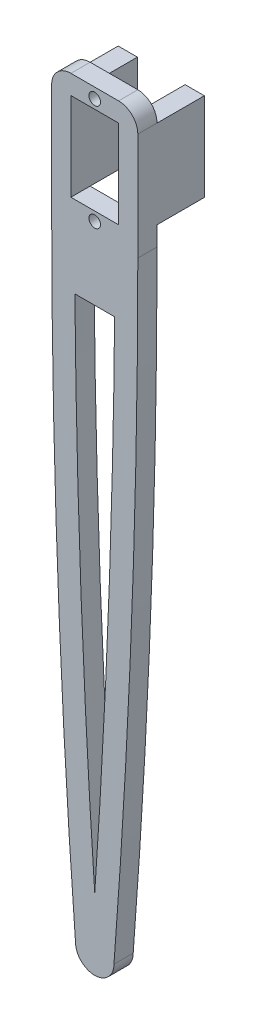
SolidWorks part; units mm, degrees
ref_plane "Front Plane" through (0, 0, 0) normal (0, 0, 1) x (1, 0, 0)
ref_plane "Top Plane" through (0, 0, 0) normal (0, 1, 0) x (1, 0, 0)
ref_plane "Right Plane" through (0, 0, 0) normal (1, 0, 0) x (0, 0, -1)
sketch "Sketch1" plane through (0, 0, 0) normal (0, 0, 1) x (1, 0, 0)
  line L0 (0, -16.45) -> (0, -173.55) construction
  line L1 (-6.2, 16.45) -> (6.2, 16.45)
  line L2 (-11.2, 11.45) -> (-11.2, -16.45)
  line L4 (11.2, 11.45) -> (11.2, -16.45)
  line L5 (-11.2, 16.45) -> (11.2, -16.45) construction
  line L6 (-11.2, -16.45) -> (11.2, 16.45) construction
  arc A1 (-5, -178.55) -> (5, -178.55) centre (0, -178.55) ccw
  arc A2 (-11.2, -16.45) -> (-5, -178.55) centre (2110.9653, -16.45) ccw
  arc A3 (11.2, -16.45) -> (5, -178.55) centre (-2110.9653, -16.45) cw
  arc A4 (11.2, 11.45) -> (6.2, 16.45) centre (6.2, 11.45) ccw
  arc A5 (-6.2, 16.45) -> (-11.2, 11.45) centre (-6.2, 11.45) ccw
  point P0 (0, 0)
  dimension "D4" = 5
  dimension "D1" = 32.9
  dimension "D2" = 22.4
  dimension "D3" = 162.1
extrude "Boss-Extrude2" add sketch "Sketch1" along normal blind 5
sketch "Sketch4" plane through (0, 0, 5) normal (0, 0, 1) x (1, 0, 0)
  line L1 (-6.2, 11.45) -> (6.2, 11.45)
  line L2 (-6.2, 11.45) -> (-6.2, -11.45)
  line L3 (-6.2, -11.45) -> (6.2, -11.45)
  line L4 (6.2, 11.45) -> (6.2, -11.45)
  line L5 (-6.2, 11.45) -> (6.2, -11.45) construction
  line L6 (-6.2, -11.45) -> (6.2, 11.45) construction
  point P0 (0, 0)
  dimension "D1" = 22.9
  dimension "D2" = 12.4
extrude "Cut-Extrude1" cut sketch "Sketch4" against normal blind 5
sketch "Sketch5" plane through (0, 0, 5) normal (0, 0, 1) x (1, 0, 0)
  line L0 (0, 0) -> (0, 13.8) construction
  line L1 (0, 0) -> (0, -13.8) construction
  circle A0 centre (0, 13.8) radius 1.5
  circle A1 centre (0, -13.8) radius 1.5
  dimension "D1" = 13.8
  dimension "D2" = 13.8
extrude "Cut-Extrude2" cut sketch "Sketch5" against normal blind 5
sketch3d "3DSketch1"
  line L6 (-5.1604, -32.6864, 5) -> (5.1604, -32.6864, 5)
  spline S2 degree 5 poles (-5.1604, -32.6864, 5) (-5.1261, -37.5289, 5) (-5.0708, -42.3713, 5) (-4.9981, -47.2135, 5) (-4.7659, -60.1446, 5) (-4.4569, -73.0738, 5) (-4.2293, -81.1606, 5) (-3.6967, -97.3316, 5) (-2.9925, -113.496, 5) (-2.6018, -121.5766, 5) (-1.8933, -135.0415, 5) (-1.1015, -148.5022, 5) (-0.7667, -153.8853, 5) (-0.4048, -159.3358, 5) (-0.0148, -164.7842, 5) (-0.0099, -164.8531, 5) (-0.0049, -164.922, 5) (0, -164.9909, 5) knots 0.10922 0.10922 0.10922 0.10922 0.10922 0.10922 0.272094 0.272094 0.272094 0.544187 0.544187 0.544187 0.816281 0.816281 0.816281 0.997676 0.997676 0.997676 1 1 1 1 1 1
  spline S3 degree 5 poles (0, -164.9909, 5) (0.0049, -164.922, 5) (0.0099, -164.8531, 5) (0.0148, -164.7842, 5) (0.4048, -159.3358, 5) (0.7667, -153.8853, 5) (1.1015, -148.5022, 5) (1.8933, -135.0415, 5) (2.6018, -121.5766, 5) (2.9925, -113.496, 5) (3.6967, -97.3316, 5) (4.2293, -81.1606, 5) (4.4569, -73.0738, 5) (4.7659, -60.1446, 5) (4.9981, -47.2135, 5) (5.0708, -42.3713, 5) (5.1261, -37.5289, 5) (5.1604, -32.6864, 5) knots 0 0 0 0 0 0 0.002324 0.002324 0.002324 0.183719 0.183719 0.183719 0.455813 0.455813 0.455813 0.727906 0.727906 0.727906 0.89078 0.89078 0.89078 0.89078 0.89078 0.89078
extrude "Cut-Extrude3" cut sketch "3DSketch1" along direction (0, 0, -1) on the side against the normal blind 5
sketch "Sketch6" plane through (0, 0, 0) normal (0, 0, -1) x (-1, 0, 0)
  line L0 (0, 0) -> (-11.2, 0) construction
  line L1 (-11.2, -16.45) -> (-11.2, 11.45) construction
  line L2 (0, 0) -> (11.2, 0) construction
  line L3 (11.2, 11.45) -> (11.2, -16.45) construction
  line L4 (-11.2, 3.2511) -> (-6.2, 3.2511) construction
  line L5 (-6.2, -11.45) -> (-6.2, 11.45) construction
  line L6 (-8.7, 3.2511) -> (-8.7, 0) construction
  line L7 (6.2, 3.2511) -> (11.2, 3.2511) construction
  line L8 (6.2, 11.45) -> (6.2, -11.45) construction
  line L9 (8.7, 3.2511) -> (8.7, 0) construction
  line L11 (-11.2, 11.45) -> (-6.2, 11.45)
  line L12 (-11.2, 11.45) -> (-11.2, -11.45)
  line L13 (-11.2, -11.45) -> (-6.2, -11.45)
  line L14 (-6.2, 11.45) -> (-6.2, -11.45)
  line L15 (-11.2, 11.45) -> (-6.2, -11.45) construction
  line L16 (-11.2, -11.45) -> (-6.2, 11.45) construction
  line L17 (6.2, 11.45) -> (11.2, 11.45)
  line L18 (6.2, 11.45) -> (6.2, -11.45)
  line L19 (6.2, -11.45) -> (11.2, -11.45)
  line L20 (11.2, 11.45) -> (11.2, -11.45)
  line L21 (6.2, 11.45) -> (11.2, -11.45) construction
  line L22 (6.2, -11.45) -> (11.2, 11.45) construction
  dimension "D1" = 22.9
  dimension "D2" = 22.9
extrude "Boss-Extrude3" add sketch "Sketch6" along normal blind 12.3
sketch "Sketch7" plane through (0, 0, -12.3) normal (0, 0, -1) x (-1, 0, 0)
  circle A0 centre (-8.6658, 0) radius 1.5
  circle A1 centre (8.8805, 0) radius 1.5
extrude "Cut-Extrude4" cut sketch "Sketch7" against normal blind 5
